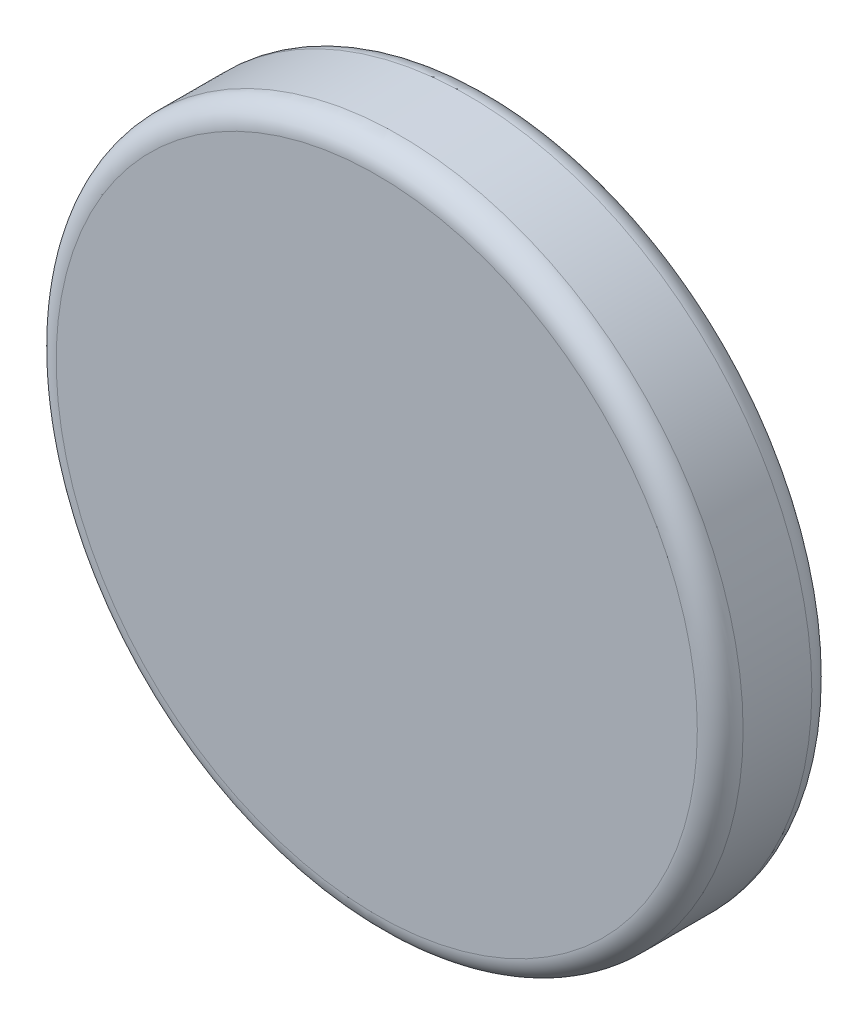
SolidWorks part; units mm, degrees
ref_plane "Front" through (0, 0, 0) normal (0, 0, 1) x (1, 0, 0)
ref_plane "Top" through (0, 0, 0) normal (0, 1, 0) x (1, 0, 0)
ref_plane "Right" through (0, 0, 0) normal (1, 0, 0) x (0, 0, -1)
sketch "Эскиз1" plane through (0, 0, 0) normal (0, 0, 1) x (1, 0, 0)
  circle A0 centre (0, 0) radius 3
  dimension "D1" = 6
extrude "Бобышка-Вытянуть1" add sketch "Эскиз1" along normal blind 1
fillet "Скругление1" radius 0.2 2 edges at (3, 0, 0) (3, 0, 1)
